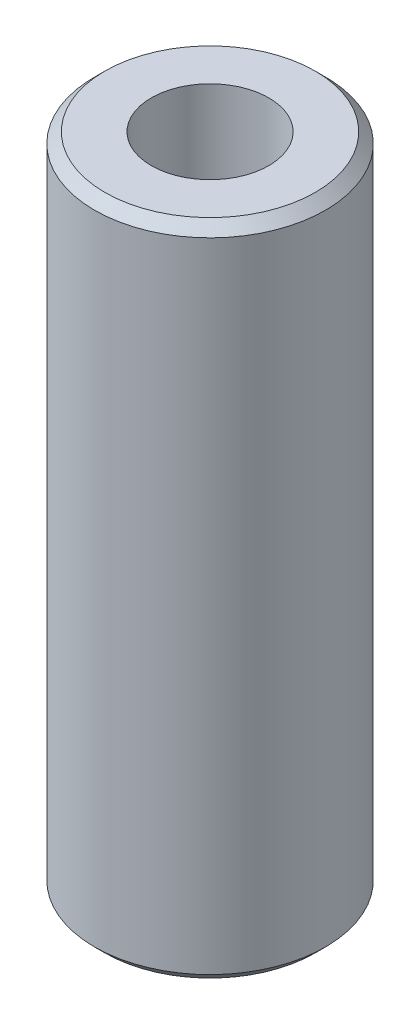
SolidWorks part; units mm, degrees
ref_plane "Front Plane" through (0, 0, 0) normal (0, 0, 1) x (1, 0, 0)
ref_plane "Top Plane" through (0, 0, 0) normal (0, 1, 0) x (1, 0, 0)
ref_plane "Right Plane" through (0, 0, 0) normal (1, 0, 0) x (0, 0, -1)
sketch "Sketch1" plane through (0, 0, 0) normal (0, 1, 0) x (1, 0, 0)
  circle A0 centre (0, 0) radius 30
  dimension "SHAFT_OD" = 60
extrude "Boss-Extrude1" add sketch "Sketch1" along normal blind 171.1599
sketch "Sketch2" plane through (0, 0, 0) normal (0, 1, 0) x (1, 0, 0)
  circle A0 centre (0, 0) radius 15.2686
  dimension "BORE_D" = 30.5372
extrude "Cut-Extrude1" cut sketch "Sketch2" along normal through all
chamfer "Chamfer1" distance 2.6712 angle 45 2 edges at (0, 171.1599, 30) (0, 0, 30)
